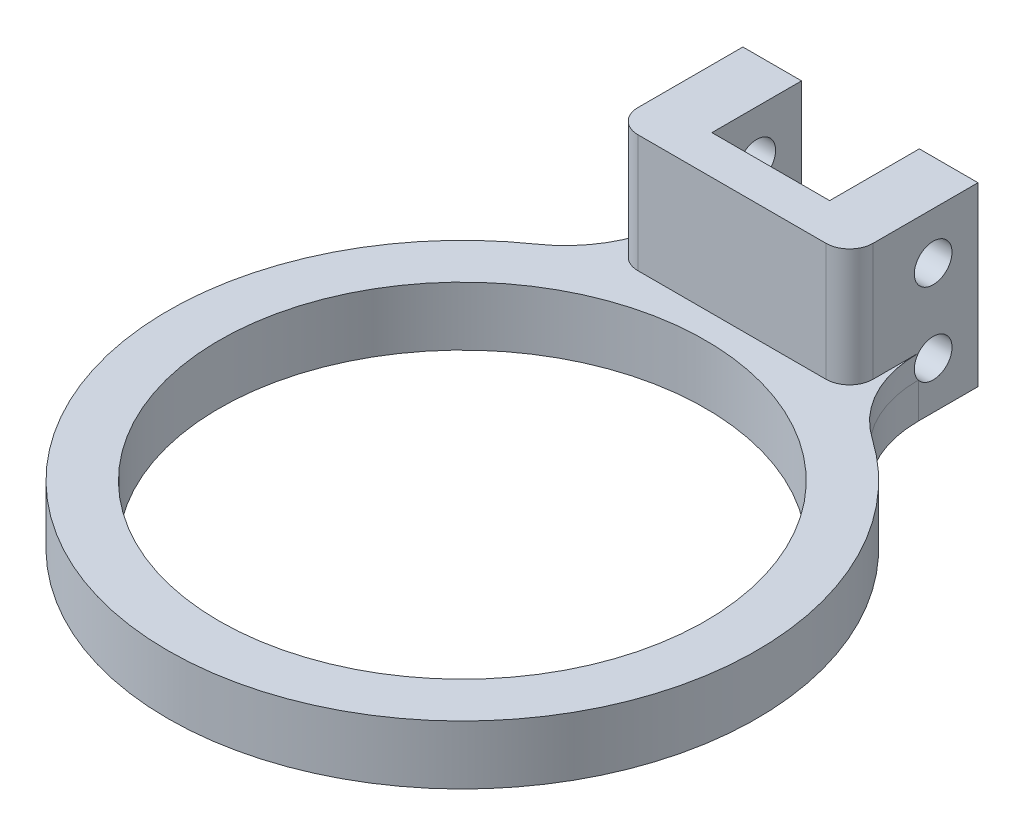
SolidWorks part; units mm, degrees
ref_plane "前视基准面" through (0, 0, 0) normal (0, 0, 1) x (1, 0, 0)
ref_plane "上视基准面" through (0, 0, 0) normal (0, 1, 0) x (1, 0, 0)
ref_plane "右视基准面" through (0, 0, 0) normal (1, 0, 0) x (0, 0, -1)
sketch "草图1" plane through (0, 0, 0) normal (0, 1, 0) x (1, 0, 0)
  circle A0 centre (0, 0) radius 20.65
  circle A2 centre (0, 0) radius 25
extrude "凸台-拉伸1" add sketch "草图1" along normal blind 5
sketch "草图2" plane through (0, 0, 0) normal (0, 1, 0) x (1, 0, 0)
  line L0 (0, 0) -> (0, 30) construction
  line L2 (-5, 33.807) -> (-9.9829, 33.807)
  line L3 (9.9829, 22.8964) -> (-9.9829, 22.8964)
  line L4 (9.9829, 22.8964) -> (9.9829, 33.807)
  line L5 (9.9829, 33.807) -> (5, 33.807)
  line L6 (-9.9829, 22.8964) -> (-9.9829, 33.807)
  line L7 (9.9829, 22.8964) -> (-9.9829, 33.807) construction
  line L8 (9.9829, 33.807) -> (-9.9829, 22.8964) construction
  line L9 (5, 26.193) -> (-5, 26.193)
  line L10 (5, 26.193) -> (5, 33.807)
  line L11 (-5, 26.193) -> (-5, 33.807)
  line L12 (5, 26.193) -> (-5, 33.807) construction
  line L13 (5, 33.807) -> (-5, 26.193) construction
  point P9 (0, 30)
  point P10 (0, 30)
extrude "凸台-拉伸2" add sketch "草图2" along normal blind 15
sketch "草图3" plane through (-9.9829, 0, 0) normal (-1, 0, 0) x (0, 0, 1)
  circle A0 centre (-30, 4) radius 1.6
  circle A1 centre (-30, 11) radius 1.6
  point P4 (0, 0)
  point P5 (0, 0)
  point P6 (0, 0)
extrude "切除-拉伸1" cut sketch "草图3" against normal through all
fillet "圆角1" radius 10 2 edges at (9.9829, 2.5, -22.9203) (-9.9829, 2.5, -22.9203)
fillet "圆角2" radius 2 2 edges at (9.9829, 10, -22.8964) (-9.9829, 10, -22.8964)
